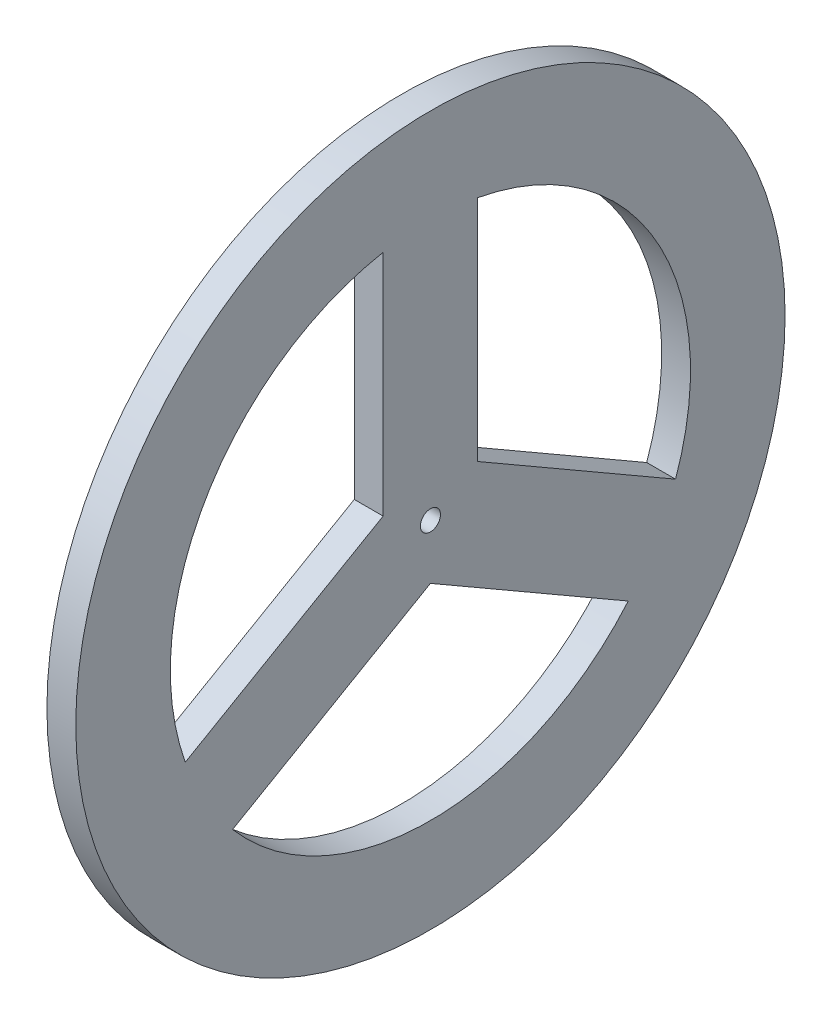
SolidWorks part; units mm, degrees
material "Corrugated Paper"
ref_plane "Front Plane" through (0, 0, 0) normal (0, 0, 1) x (1, 0, 0)
ref_plane "Top Plane" through (0, 0, 0) normal (0, 1, 0) x (1, 0, 0)
ref_plane "Right Plane" through (0, 0, 0) normal (1, 0, 0) x (0, 0, -1)
sketch "Sketch2" plane through (0, 0, 0) normal (1, 0, 0) x (0, 0, -1)
  line L0 (0, 27.94) -> (0, 0) construction
  line L1 (0, 0) -> (24.1967, -13.97) construction
  line L2 (0, 0) -> (-24.1967, -13.97) construction
  line L3 (-2.54, -4.3994) -> (21.6567, -18.3694)
  line L4 (-2.54, 4.3994) -> (-26.7367, -9.5706)
  line L5 (-5.08, 27.94) -> (-5.08, 0)
  line L6 (2.54, 4.3994) -> (26.7367, -9.5706)
  line L7 (2.54, -4.3994) -> (-21.6567, -18.3694)
  line L8 (5.08, 27.94) -> (5.08, 0)
  circle A0 centre (0, 0) radius 38.1
  circle A1 centre (0, 0) radius 27.94
  circle A2 centre (0, 0) radius 5.08
  circle A3 centre (0, 0) radius 1.0795
  dimension "D1" = 76.2
  dimension "D3" = 10.16
  dimension "D4" = 2.159
  dimension "D5" = 120
  dimension "D6" = 120
  dimension "D2" = 10.16
  dimension "D7" = 5.08
  dimension "D8" = 5.08
extrude "Boss-Extrude5" add sketch "Sketch2" along normal blind 3.0988 contours A0
extrude "Cut-Extrude3" cut sketch "Sketch2<3>" along direction (1, 0, 0) on the side of the normal through all contours L7 A1 L3 | L5 A1 L4 | L6 A1 L8 | A3 region at (0, -18.2942, 0) region at (0, 9.1471, 15.8433) region at (0, 9.1471, -15.8433) region at (0, 0, 0)
sketch "Sketch2<3>" plane through (0, 0, 0) normal (1, 0, 0) x (0, 0, -1) same geometry as "Sketch2"
equation "\"rodThick\"= 0.085in"
equation "\"thick\"= 0.122in"
equation "\"D1@Boss-Extrude5\"=\"thick\""
equation "\"D4@Sketch2\"=\"rodThick\""
